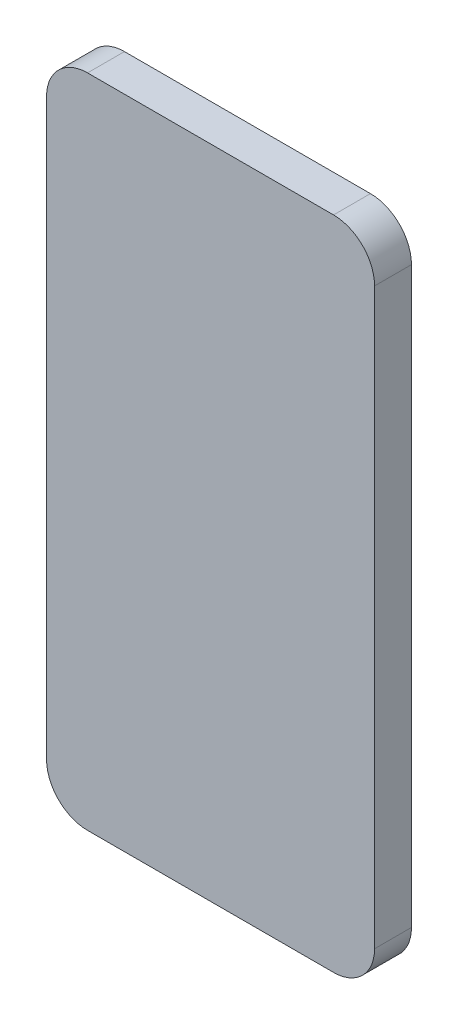
SolidWorks part; units mm, degrees
ref_plane "前视基准面" through (0, 0, 0) normal (0, 0, 1) x (1, 0, 0)
ref_plane "上视基准面" through (0, 0, 0) normal (0, 1, 0) x (1, 0, 0)
ref_plane "右视基准面" through (0, 0, 0) normal (1, 0, 0) x (0, 0, -1)
sketch "草图1" plane through (0, 0, 0) normal (0, 0, 1) x (1, 0, 0)
  line L1 (-39.1736, 40.6612) -> (40.8264, 40.6612)
  line L2 (-39.1736, 40.6612) -> (-39.1736, -119.3388)
  line L3 (-39.1736, -119.3388) -> (40.8264, -119.3388)
  line L4 (40.8264, 40.6612) -> (40.8264, -119.3388)
  dimension "D1" = 80
  dimension "D2" = 160
extrude "凸台-拉伸1" add sketch "草图1" along normal blind 9
fillet "圆角1" radius 10 1 edges at (-39.1736, 40.6612, 4.5) type face fillet first side face at (0.8264, 40.6612, 4.5) second side face at (-39.1736, -39.3388, 4.5)
fillet "圆角2" radius 10 1 edges at (40.8264, 40.6612, 4.5) type face fillet first side face at (5.8264, 40.6612, 4.5) second side face at (40.8264, -39.3388, 4.5)
fillet "圆角3" radius 10 1 edges at (40.8264, -119.3388, 4.5) type face fillet first side face at (40.8264, -44.3388, 4.5) second side face at (0.8264, -119.3388, 4.5)
fillet "圆角4" radius 10 1 edges at (-39.1736, -119.3388, 4.5) type face fillet first side face at (-4.1736, -119.3388, 4.5) second side face at (-39.1736, -44.3388, 4.5)
